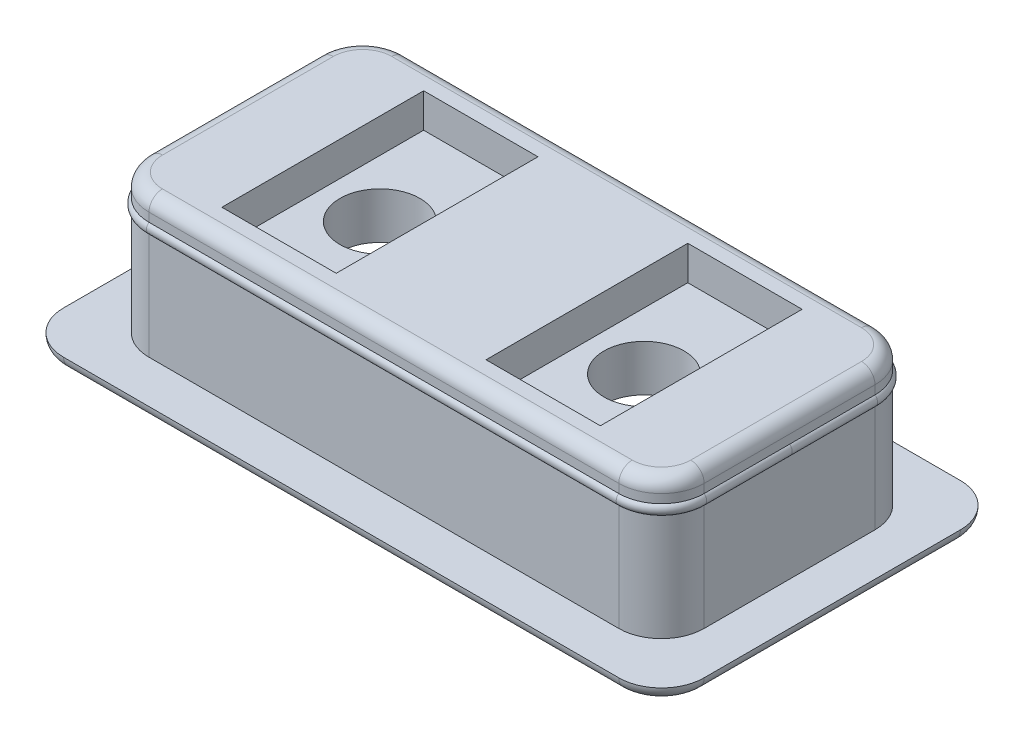
SolidWorks part; units mm, degrees
ref_plane "Front Plane" through (0, 0, 0) normal (0, 0, 1) x (1, 0, 0)
ref_plane "Top Plane" through (0, 0, 0) normal (0, 1, 0) x (1, 0, 0)
ref_plane "Right Plane" through (0, 0, 0) normal (1, 0, 0) x (0, 0, -1)
sketch "Sketch1" plane through (0, 0, 0) normal (0, 1, 0) x (1, 0, 0)
  line L1 (41.275, 19.05) -> (-41.275, 19.05)
  line L2 (41.275, 19.05) -> (41.275, -19.05)
  line L3 (41.275, -19.05) -> (-41.275, -19.05)
  line L4 (-41.275, 19.05) -> (-41.275, -19.05)
  line L5 (41.275, 19.05) -> (-41.275, -19.05) construction
  line L6 (41.275, -19.05) -> (-41.275, 19.05) construction
  point P0 (0, 0)
  dimension "D1" = 38.1
  dimension "D2" = 82.55
extrude "Boss-Extrude1" add sketch "Sketch1" along normal blind 12.7
sketch "Sketch2" plane through (0, 0, 0) normal (0, -1, 0) x (1, 0, 0)
  line L12 (-47.625, 25.4) -> (-47.625, -25.4)
  line L13 (-47.625, -25.4) -> (47.625, -25.4)
  line L14 (47.625, -25.4) -> (47.625, 25.4)
  line L15 (47.625, 25.4) -> (-47.625, 25.4)
  line L16 (-47.625, 25.4) -> (-47.625, -25.4)
  line L17 (-47.625, -25.4) -> (47.625, -25.4)
  line L18 (47.625, -25.4) -> (47.625, 25.4)
  line L19 (47.625, 25.4) -> (-47.625, 25.4)
  dimension "D1" = 6.35
extrude "Boss-Extrude2" add sketch "Sketch2" against normal blind 2
shell "Shell1" thickness 2 removed face at (0, 0, 0)
sketch "Sketch3" plane through (0, 10.7, 0) normal (0, -1, 0) x (1, 0, 0)
  line L0 (0, 0) -> (0, -17.05) construction
  line L6 (-27.2625, 14.6) -> (-12.0125, 14.6) construction
  line L11 (-27.2625, 14.6) -> (-27.2625, -14.6) construction
  line L12 (-27.2625, -14.6) -> (-12.0125, -14.6) construction
  line L17 (-12.0125, 14.6) -> (-12.0125, -14.6) construction
  line L18 (-27.2625, 14.6) -> (-12.0125, -14.6) construction
  line L23 (-27.2625, -14.6) -> (-12.0125, 14.6) construction
  line L25 (-39.275, -17.05) -> (39.275, -17.05) construction
  circle A0 centre (-19.6375, 0) radius 5.95
  circle A1 centre (19.6375, 0) radius 5.95
  dimension "D3" = 39.275
  dimension "D4" = 11.9
  dimension "D1" = 29.2
  dimension "D2" = 15.25
extrude "Cut-Extrude1" cut sketch "Sketch3" against normal through all both and the other way through all
fillet "Fillet1" radius 6.35 12 edges at (-47.625, 1, 25.4) (-47.625, 1, -25.4) (47.625, 1, -25.4) (47.625, 1, 25.4) (-41.275, 7.35, -19.05) (41.275, 7.35, -19.05) (-41.275, 7.35, 19.05) (41.275, 7.35, 19.05) (-39.275, 5.35, 17.05) (39.275, 5.35, 17.05) (-39.275, 5.35, -17.05) (39.275, 5.35, -17.05)
fillet "Fillet2" radius 2 16 edges at (45.7651, 0, 23.5401) (47.625, 0, 0) (45.7651, 0, -23.5401) (0, 0, -25.4) (-45.7651, 0, -23.5401) (-47.625, 0, 0) (-45.7651, 0, 23.5401) (0, 0, 25.4) (39.275, 0, 0) (0, 0, 17.05) (-39.275, 0, 0) (0, 0, -17.05) (37.4151, 0, -15.1901) (37.4151, 0, 15.1901) (-37.4151, 0, 15.1901) (-37.4151, 0, -15.1901)
sketch "Sketch4" plane through (0, 12.7, 0) normal (0, 1, 0) x (1, 0, 0)
  line L10 (11.1375, -15) -> (28.1375, -15)
  line L11 (11.1375, -15) -> (11.1375, 15)
  line L12 (11.1375, 15) -> (28.1375, 15)
  line L13 (28.1375, -15) -> (28.1375, 15)
  line L14 (11.1375, -15) -> (28.1375, 15) construction
  line L15 (11.1375, 15) -> (28.1375, -15) construction
  line L37 (-28.1375, -15) -> (-11.1375, -15)
  line L38 (-28.1375, -15) -> (-28.1375, 15)
  line L39 (-28.1375, 15) -> (-11.1375, 15)
  line L40 (-11.1375, -15) -> (-11.1375, 15)
  line L41 (-28.1375, -15) -> (-11.1375, 15) construction
  line L42 (-28.1375, 15) -> (-11.1375, -15) construction
  line L44 (34.925, 19.05) -> (-34.925, 19.05)
  line L45 (-41.275, 12.7) -> (-41.275, -12.7)
  line L46 (-34.925, -19.05) -> (34.925, -19.05)
  line L47 (41.275, -12.7) -> (41.275, 12.7)
  line L48 (34.925, 19.05) -> (-34.925, 19.05)
  line L49 (-41.275, 12.7) -> (-41.275, -12.7)
  line L50 (-34.925, -19.05) -> (34.925, -19.05)
  line L51 (41.275, -12.7) -> (41.275, 12.7)
  arc A4 (-34.925, 19.05) -> (-41.275, 12.7) centre (-34.925, 12.7) ccw
  arc A5 (-41.275, -12.7) -> (-34.925, -19.05) centre (-34.925, -12.7) ccw
  arc A6 (34.925, -19.05) -> (41.275, -12.7) centre (34.925, -12.7) ccw
  arc A7 (41.275, 12.7) -> (34.925, 19.05) centre (34.925, 12.7) ccw
  arc A8 (-34.925, 19.05) -> (-41.275, 12.7) centre (-34.925, 12.7) ccw
  arc A9 (-41.275, -12.7) -> (-34.925, -19.05) centre (-34.925, -12.7) ccw
  arc A10 (34.925, -19.05) -> (41.275, -12.7) centre (34.925, -12.7) ccw
  arc A11 (41.275, 12.7) -> (34.925, 19.05) centre (34.925, 12.7) ccw
  point P12 (19.6375, 0)
  point P45 (-19.6375, 0)
  dimension "D1" = 0
  dimension "D3" = 30
  dimension "D4" = 17
extrude "Boss-Extrude3" add sketch "Sketch4" along normal blind 9.98
sketch "Sketch5" plane through (0, 0, 0) normal (0, 0, 1) x (1, 0, 0)
  line L5 (41.275, 2) -> (41.275, 22.68) construction
  line L6 (47.625, 2) -> (41.275, 2) construction
  line L7 (41.275, 19.375) -> (41.275, 17.875)
  arc A0 (41.275, 19.375) -> (41.275, 17.875) centre (40.7273, 18.625) cw
  point P8 (41.656, 18.625)
  dimension "D1" = 15.875
  dimension "D2" = 0.381
  dimension "D3" = 1.5
sketch "Sketch6" plane through (0, 22.68, 0) normal (0, 1, 0) x (1, 0, 0)
  line L4 (34.925, 19.05) -> (-34.925, 19.05)
  line L5 (-41.275, 12.7) -> (-41.275, -12.7)
  line L6 (-34.925, -19.05) -> (34.925, -19.05)
  line L7 (41.275, -12.7) -> (41.275, 12.7)
  line L8 (34.925, 19.05) -> (-34.925, 19.05)
  line L9 (-41.275, 12.7) -> (-41.275, -12.7)
  line L10 (-34.925, -19.05) -> (34.925, -19.05)
  line L11 (41.275, -12.7) -> (41.275, 12.7)
  arc A4 (41.275, 12.7) -> (34.925, 19.05) centre (34.925, 12.7) ccw
  arc A5 (-34.925, 19.05) -> (-41.275, 12.7) centre (-34.925, 12.7) ccw
  arc A6 (-41.275, -12.7) -> (-34.925, -19.05) centre (-34.925, -12.7) ccw
  arc A7 (34.925, -19.05) -> (41.275, -12.7) centre (34.925, -12.7) ccw
  arc A8 (41.275, 12.7) -> (34.925, 19.05) centre (34.925, 12.7) ccw
  arc A9 (-34.925, 19.05) -> (-41.275, 12.7) centre (-34.925, 12.7) ccw
  arc A10 (-41.275, -12.7) -> (-34.925, -19.05) centre (-34.925, -12.7) ccw
  arc A11 (34.925, -19.05) -> (41.275, -12.7) centre (34.925, -12.7) ccw
  dimension "D1" = 0
sweep "Sweep1" add profiles "Sketch5" path "Sketch6"
fillet "Fillet4" radius 2 8 edges at (-39.4151, 22.68, 17.1901) (-41.275, 22.68, 0) (-39.4151, 22.68, -17.1901) (0, 22.68, -19.05) (39.4151, 22.68, -17.1901) (41.275, 22.68, 0) (39.4151, 22.68, 17.1901) (0, 22.68, 19.05)
sketch "Sketch7" plane through (0, 12.7, 0) normal (0, 1, 0) x (1, 0, 0)
  line L4 (11.1375, -15) -> (28.1375, -15)
  line L5 (28.1375, -15) -> (28.1375, 15)
  line L6 (28.1375, 15) -> (11.1375, 15)
  line L7 (11.1375, 15) -> (11.1375, -15)
  line L8 (11.1375, -15) -> (28.1375, -15)
  line L9 (28.1375, -15) -> (28.1375, 15)
  line L10 (28.1375, 15) -> (11.1375, 15)
  line L11 (11.1375, 15) -> (11.1375, -15)
  line L12 (-28.1375, -15) -> (-11.1375, -15)
  line L13 (-11.1375, -15) -> (-11.1375, 15)
  line L14 (-11.1375, 15) -> (-28.1375, 15)
  line L15 (-28.1375, 15) -> (-28.1375, -15)
  line L16 (-28.1375, -15) -> (-11.1375, -15)
  line L17 (-11.1375, -15) -> (-11.1375, 15)
  line L18 (-11.1375, 15) -> (-28.1375, 15)
  line L19 (-28.1375, 15) -> (-28.1375, -15)
  circle A0 centre (19.6375, 0) radius 5.95 construction
  circle A1 centre (-19.6375, 0) radius 5.95 construction
  circle A2 centre (19.6375, 0) radius 5.95
  circle A3 centre (-19.6375, 0) radius 5.95
  dimension "D1" = 0
  dimension "D2" = 0
extrude "Boss-Extrude4" add sketch "Sketch7" along normal offset from surface (4.9 mm away) 6.9 up to face at (-19.6375, 10.7, -5.95)
